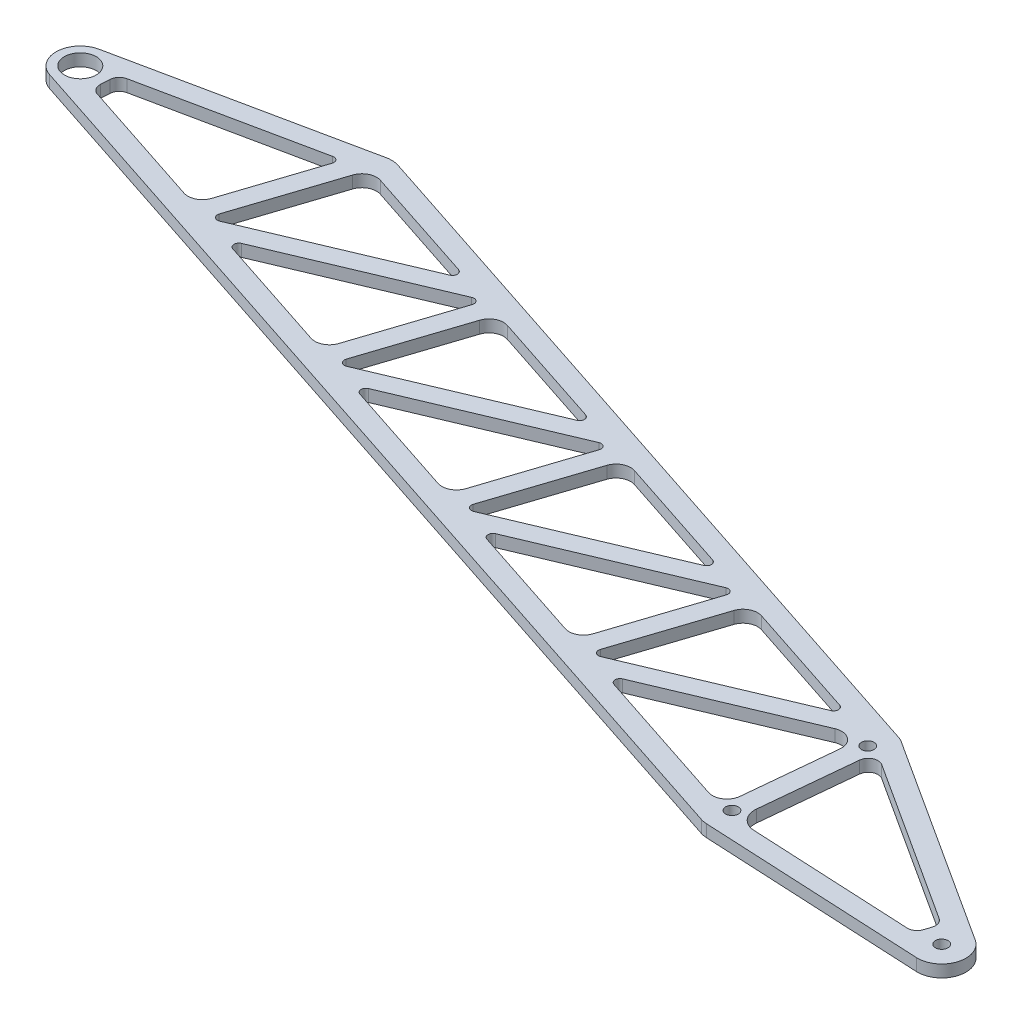
SolidWorks part; units mm, degrees
material "6061-T6 (SS)"
ref_plane "Front Plane" through (0, 0, 0) normal (0, 0, 1) x (1, 0, 0)
ref_plane "Top Plane" through (0, 0, 0) normal (0, 1, 0) x (1, 0, 0)
ref_plane "Right Plane" through (0, 0, 0) normal (1, 0, 0) x (0, 0, -1)
sketch "Sketch2" plane through (0, 0, 0) normal (0, 1, 0) x (1, 0, 0)
  line L0 (-3.9656, -12.065) -> (504.1341, -179.0714)
  line L13 (507.4701, -179.6908) -> (623.0025, -185.4258)
  line L14 (630.5196, -162.0713) -> (521.2932, -91.5668)
  line L17 (121.7158, 38.413) -> (-2.5982, 12.4314)
  line L18 (128.2796, 38.0466) -> (518.3713, -90.172)
  circle A0 centre (0, 0) radius 8.3344
  circle A1 centre (0, 0) radius 12.7 construction
  circle A2 centre (508.0997, -167.0065) radius 12.7 construction
  circle A3 centre (623.6321, -172.7414) radius 3.302
  circle A4 centre (508.0997, -167.0065) radius 3.302
  circle A5 centre (623.6321, -172.7414) radius 12.7 construction
  arc A6 (504.1341, -179.0714) -> (507.4701, -179.6908) centre (508.0997, -167.0065) ccw
  arc A7 (630.5196, -162.0713) -> (623.0025, -185.4258) centre (623.6321, -172.7414) cw
  arc A8 (-2.5982, 12.4314) -> (-3.9656, -12.065) centre (0, 0) ccw
  circle A9 centre (514.4057, -102.237) radius 12.7 construction
  arc A10 (518.3713, -90.172) -> (521.2932, -91.5668) centre (514.4057, -102.237) cw
  circle A11 centre (514.4057, -102.237) radius 3.302
  circle A12 centre (124.3139, 25.9816) radius 12.7 construction
  arc A13 (121.7158, 38.413) -> (128.2796, 38.0466) centre (124.3139, 25.9816) cw
  dimension "D1" = 25.4
  dimension "D2" = 16.6687
  dimension "D3" = 30
  dimension "D4" = 30
  dimension "D5" = 88.9
extrude "Boss-Extrude1" add sketch "Sketch2" along normal blind 3.175 and the other way blind 3.175 contours A0 | A3 | A4 | A11 | L18 A10 L14 A7 L13 A6 L0 A8 L17 A13
sketch "Sketch4" plane through (0, 3.175, 0) normal (0, 1, 0) x (1, 0, 0)
  line L3 (123.1736, 29.0302) -> (101.7592, -36.1208)
  line L4 (101.7592, -36.1208) -> (197.8837, 4.4738)
  line L5 (197.8837, 4.4738) -> (123.1736, 29.0302)
  line L6 (212.5693, -0.3532) -> (116.4448, -40.9477)
  line L7 (116.4448, -40.9477) -> (191.1549, -65.5041)
  line L8 (191.1549, -65.5041) -> (212.5693, -0.3532)
  line L9 (222.2212, -3.5257) -> (200.8069, -68.6766)
  line L10 (200.8069, -68.6766) -> (296.9314, -28.082)
  line L11 (296.9314, -28.082) -> (222.2212, -3.5257)
  line L12 (311.6169, -32.909) -> (215.4924, -73.5035)
  line L13 (215.4924, -73.5035) -> (290.2025, -98.0599)
  line L14 (290.2025, -98.0599) -> (311.6169, -32.909)
  line L33 (321.2689, -36.0815) -> (299.8545, -101.2324)
  line L34 (299.8545, -101.2324) -> (395.979, -60.6378)
  line L35 (395.979, -60.6378) -> (321.2689, -36.0815)
  line L36 (410.6645, -65.4648) -> (314.5401, -106.0593)
  line L37 (314.5401, -106.0593) -> (389.2502, -130.6157)
  line L38 (389.2502, -130.6157) -> (410.6645, -65.4648)
  line L39 (519.4849, -102.4923) -> (512.9328, -169.7895)
  line L40 (512.9328, -169.7895) -> (604.5707, -174.3384)
  line L41 (609.0809, -160.3256) -> (519.4849, -102.4923)
  line L42 (509.7122, -98.0206) -> (413.5877, -138.6151)
  line L43 (413.5877, -138.6151) -> (502.9017, -167.9716)
  line L44 (502.9017, -167.9716) -> (509.7122, -98.0206)
  line L45 (420.3165, -68.6373) -> (398.9022, -133.7882)
  line L46 (398.9022, -133.7882) -> (495.0266, -93.1936)
  line L47 (495.0266, -93.1936) -> (420.3165, -68.6373)
  line L48 (-3.9656, -12.065) -> (504.1341, -179.0714) construction
  line L49 (128.2796, 38.0466) -> (518.3713, -90.172) construction
  line L53 (22.6777, 7.3345) -> (111.4458, 25.8871)
  line L54 (111.4458, 25.8871) -> (92.1073, -32.9483)
  line L55 (92.1073, -32.9483) -> (21.7204, -9.8129)
  line L56 (121.7158, 38.413) -> (-2.5982, 12.4314) construction
  line L58 (630.5196, -162.0713) -> (521.2932, -91.5668) construction
  line L59 (507.4701, -179.6908) -> (623.0025, -185.4258) construction
  line L60 (514.4057, -102.237) -> (508.0997, -167.0065) construction
  line L61 (609.0809, -160.3256) -> (614.555, -163.8591)
  line L62 (604.5707, -174.3384) -> (611.0781, -174.6614)
  line L63 (22.6777, 7.3345) -> (14.1894, 5.5605)
  line L64 (21.7204, -9.8129) -> (13.4824, -7.1052)
  line L66 (14.1894, 5.5605) -> (13.4824, -7.1052)
  line L67 (614.555, -163.8591) -> (611.0781, -174.6614)
  dimension "D1" = 10.16
  dimension "D2" = 10.16
  dimension "D3" = 10.16
  dimension "D4" = 10.16
  dimension "D5" = 10.16
  dimension "D6" = 10.16
  dimension "D7" = 10.16
  dimension "D8" = 10.16
  dimension "D9" = 10.16
  dimension "D10" = 10.16
  dimension "D11" = 10.16
  dimension "D12" = 10.16
  dimension "D13" = 10.16
  dimension "0.4" = 10.16
  dimension "D14" = 10.16
  dimension "D15" = 10.16
  dimension "D16" = 10.16
  dimension "D17" = 10.16
  dimension "D18" = 10.16
  dimension "D19" = 10.16
  dimension "D20" = 10.16
  dimension "D21" = 10.16
  dimension "D22" = 10.16
  dimension "D23" = 10.16
  dimension "D24" = 10.16
  dimension "D25" = 10.16
  dimension "D26" = 10.16
  dimension "D27" = 10.16
  dimension "D28" = 10.16
  dimension "D29" = 97.79
  dimension "D30" = 5.08
extrude "Cut-Extrude1" cut sketch "Sketch4" against normal through all
fillet "right angles" radius 7.62 9 edges at (420.3165, 0, 68.6373) (321.2689, 0, 36.0815) (389.2502, 0, 130.6157) (502.9017, 0, 167.9716) (290.2025, 0, 98.0599) (222.2212, 0, 3.5257) (191.1549, 0, 65.5041) (123.1736, 0, -29.0302) (92.1073, 0, 32.9483)
fillet "Fillet9" radius 9.398 1 edges at (512.9328, 0, 169.7895)
fillet "Fillet10" radius 7.62 1 edges at (509.7122, 0, 98.0206)
fillet "Fillet11" radius 5.08 1 edges at (519.4849, 0, 102.4923)
fillet "Fillet13" radius 5.08 4 edges at (614.555, 0, 163.8591) (611.0781, 0, 174.6614) (13.4824, 0, 7.1052) (14.1894, 0, -5.5605)
fillet "Fillet14" radius 2.54 16 edges at (410.6645, 0, 65.4648) (311.6169, 0, 32.909) (413.5877, 0, 138.6151) (215.4924, 0, 73.5035) (314.5401, 0, 106.0593) (398.9022, 0, 133.7882) (299.8545, 0, 101.2324) (200.8069, 0, 68.6766) (212.5693, 0, 0.3532) (101.7592, 0, 36.1208) (116.4448, 0, 40.9477) (495.0266, 0, 93.1936) (395.979, 0, 60.6378) (296.9314, 0, 28.082) (197.8837, 0, -4.4738) (111.4458, 0, -25.8871)
